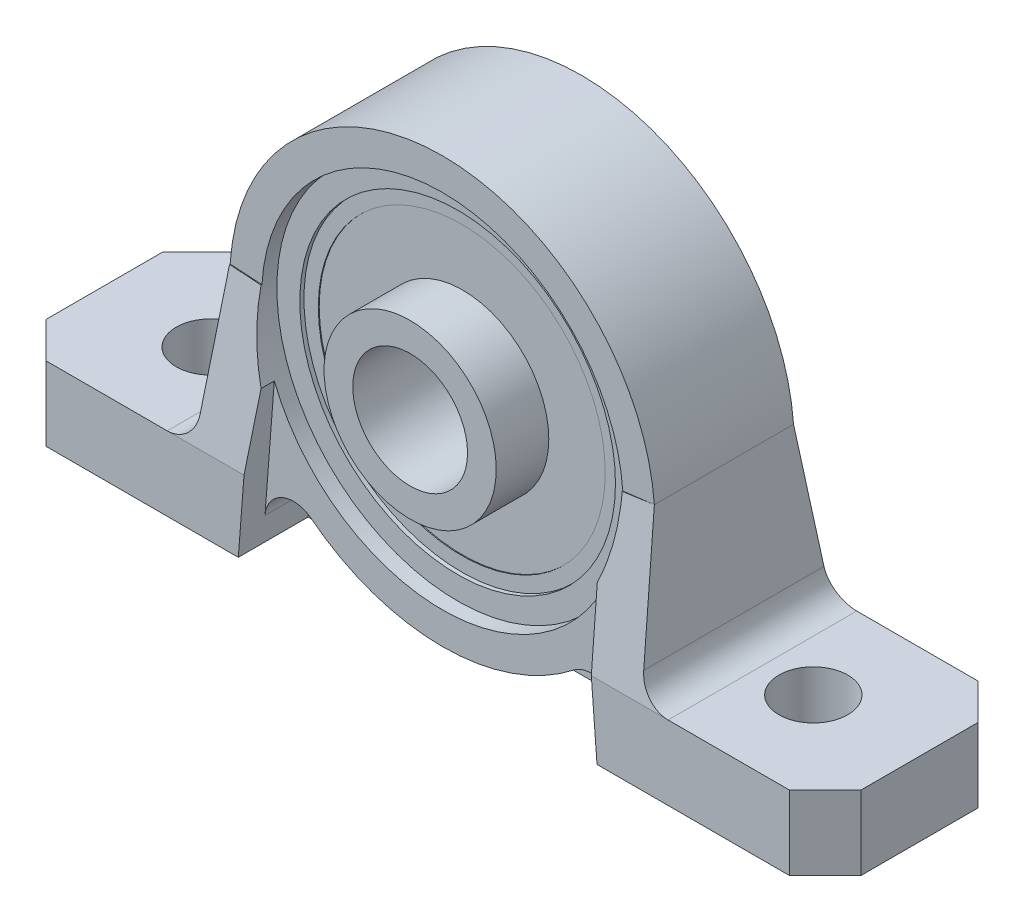
SolidWorks part; units mm, degrees
ref_plane "Front Plane" through (0, 0, 0) normal (0, 0, 1) x (1, 0, 0)
ref_plane "Top Plane" through (0, 0, 0) normal (0, 1, 0) x (1, 0, 0)
ref_plane "Right Plane" through (0, 0, 0) normal (1, 0, 0) x (0, 0, -1)
sketch "Sketch1" plane through (0, 0, 0) normal (1, 0, 0) x (0, 0, -1)
  line L0 (0, 17.3097) -> (0, -17.576) construction
  line L1 (0, 6) -> (-3.4358, 6)
  line L2 (-3.4358, 6) -> (-3.4358, 10)
  line L3 (-3.4358, 10) -> (3.4358, 10)
  line L4 (3.4358, 10) -> (3.4358, 6)
  line L5 (3.4358, 6) -> (0, 6)
  line L6 (-3.4358, 10) -> (-3.5, 10)
  line L7 (-3.5, 10) -> (-3.5, 11)
  line L8 (-3.5, 11) -> (0, 11)
  line L9 (0, 11) -> (3.5, 11)
  line L10 (3.5, 11) -> (3.5, 10)
  line L11 (3.5, 10) -> (3.4358, 10)
  line L12 (-11.6276, 0) -> (16.2204, 0) construction
  line L13 (3.4358, 6) -> (3.5, 6)
  line L14 (3.5, 6) -> (3.5, 4)
  line L15 (3.5, 4) -> (-7.0985, 4)
  line L16 (-7.0985, 4) -> (-7.0985, 6)
  line L17 (-7.0985, 6) -> (-3.4358, 6)
  line L18 (-3.5, 11) -> (-3.7892, 11)
  line L19 (-3.7892, 11) -> (-3.7892, 12.6)
  line L20 (-3.7892, 12.6) -> (0, 12.6)
  line L21 (0, 12.6) -> (3.7892, 12.6)
  line L22 (3.7892, 12.6) -> (3.7892, 11)
  line L23 (3.7892, 11) -> (3.5, 11)
  line L24 (-3.7892, 12.6) -> (-4.85, 12.6)
  line L25 (-4.85, 12.6) -> (-4.85, 14.815)
  line L26 (-4.85, 14.815) -> (0, 14.815)
  line L27 (0, 14.815) -> (4.85, 14.815)
  line L28 (4.85, 14.815) -> (4.85, 12.6)
  line L29 (4.85, 12.6) -> (3.7892, 12.6)
  point P15 (4.1728, 12.6)
  point P30 (3.7892, 12.6)
  point P31 (-4.85, 12.6)
  dimension "D1" = 7
  dimension "D2" = 22
  dimension "D3" = 8
  dimension "D4" = 2
  dimension "D5" = 1
  dimension "D6" = 1.6
  dimension "D7" = 29.63
  dimension "D8" = 9.7
revolve "Revolve1" add sketch "Sketch1" angle 360 about L12 region at (0, 5, 1.7993) region at (0, 8, 0) region at (0, 10.5, 0) region at (0, 11.8, 0) region at (0, 13.7075, 0)
sketch "Sketch2" plane through (0, 0, 0) normal (0, 0, 1) x (1, 0, 0)
  line L0 (0, 20.5844) -> (0, -27.498) construction
  line L1 (14.7714, 1.1362) -> (15.6015, -9.655)
  line L2 (15.6015, -9.655) -> (28.4021, -9.655)
  line L3 (28.4021, -9.655) -> (28.4021, -14.815)
  line L4 (28.4021, -14.815) -> (12.5, -14.815)
  line L5 (12.5, -14.815) -> (11.7155, -4.6375)
  line L6 (15.6015, -9.655) -> (12.1023, -9.655)
  line L7 (-15.6015, -9.655) -> (-12.1023, -9.655)
  line L8 (-12.5, -14.815) -> (-11.7155, -4.6375)
  line L9 (-28.4021, -14.815) -> (-12.5, -14.815)
  line L10 (-28.4021, -9.655) -> (-28.4021, -14.815)
  line L11 (-15.6015, -9.655) -> (-28.4021, -9.655)
  line L12 (-14.7714, 1.1362) -> (-15.6015, -9.655)
  line L13 (-12.5, -14.815) -> (12.5, -14.815) construction
  circle A0 centre (0, 0) radius 14.815 construction
  circle A1 centre (0, 0) radius 12.6 construction
  arc A2 (14.7714, 1.1362) -> (-14.7714, 1.1362) centre (0, 0) ccw
  arc A3 (11.7155, -4.6375) -> (-11.7155, -4.6375) centre (0, 0) ccw
  circle A4 centre (0, 0) radius 12.6 construction
  point P12 (0, -14.815)
  dimension "D3" = 5.16
  dimension "D4" = 25
extrude "Boss-Extrude1" add sketch "Sketch2" along normal mid plane 13.15 contours L2 L6 L5 L4 L3 | A2 L0 A3 L5 L6 L1 | L0 A2 L12 L7 L8 A3 | L7 L11 L10 L9 L8 region at (14.791, -4.2898, 0) region at (20.3512, -12.2244, 0) region at (-20.3512, -12.2244, 0)
sketch "Sketch8" plane through (0, -9.655, 0) normal (0, 1, 0) x (1, 0, 0)
  line L0 (-34.4299, 0) -> (37.1914, 0) construction
  line L1 (0, 17.012) -> (0, -19.2394) construction
  circle A0 centre (21, 0) radius 2.4
  circle A1 centre (-21, 0) radius 2.4
  dimension "D1" = 4.8
  dimension "D2" = 42
extrude "Cut-Extrude3" cut sketch "Sketch8" against normal through all
chamfer "Chamfer1" distance 2.5 angle 45 4 edges at (28.4021, -12.235, -6.575) (28.4021, -12.235, 6.575) (-28.4021, -12.235, -6.575) (-28.4021, -12.235, 6.575)
sketch "Sketch9" plane through (0, 0, 0) normal (0, 0, 1) x (1, 0, 0)
  line L0 (-12.5, -14.815) -> (12.5, -14.815)
  line L1 (12.5, -14.815) -> (11.7155, -4.6375)
  line L2 (-12.5, -14.815) -> (-11.7155, -4.6375)
  arc A0 (-11.7155, -4.6375) -> (11.7155, -4.6375) centre (0, 0) ccw
extrude "Boss-Extrude2" add sketch "Sketch9" along normal mid plane 3.42
fillet "Fillet1" radius 2 4 edges at (-12.0251, -8.6534, -3.28) (12.0251, -8.6534, -3.28) (-12.0251, -8.6534, 3.28) (12.0251, -8.6534, 3.28)
sketch "Sketch13" plane through (0, 0, 6.575) normal (0, 0, 1) x (1, 0, 0)
  line L0 (-11.89, 0.7057) -> (-17.6102, 1.0452)
  line L1 (-17.6102, 1.0452) -> (-14.4258, 15.1892)
  line L2 (-14.4258, 15.1892) -> (3.1299, 17.3837)
  line L3 (3.1299, 17.3837) -> (21.4172, 11.678)
  line L4 (21.4172, 11.678) -> (16.7844, 1.3884)
  line L5 (16.7844, 1.3884) -> (11.9408, 0.783)
  line L6 (11.9408, 0.783) -> (0.5941, 11.678)
  line L7 (0.5941, 11.678) -> (-11.89, 0.7057)
extrude "Cut-Extrude4" cut sketch "Sketch13" against normal up to surface (1.725 mm away) up to face at (0, -11.3237, 4.85)
extrude "Cut-Extrude5" cut sketch "Sketch13<2>" against normal through all from surface starting at face at (0, -11.3237, -4.85)
sketch "Sketch13<2>" plane through (0, 0, 6.575) normal (0, 0, 1) x (1, 0, 0) same geometry as "Sketch13"
sketch "Sketch14" plane through (0, 0, 0) normal (1, 0, 0) x (0, 0, -1)
  line L0 (-4.85, 1.1368) -> (-6.575, -9.655)
  line L1 (-6.575, -9.655) -> (-6.575, -14.815)
  line L2 (-6.575, -14.815) -> (6.575, -14.815)
  line L3 (6.575, -14.815) -> (6.575, -9.655)
  line L4 (6.575, -9.655) -> (4.85, 1.1368)
  line L6 (-4.85, 1.1368) -> (-4.85, 17.5008)
  line L7 (-4.85, 17.5008) -> (4.85, 17.5008)
  line L8 (4.85, 17.5008) -> (4.85, 1.1368)
extrude "Cut-Extrude-Thin5" cut sketch "Sketch14" along normal through all from offset 7 thin thin type one direction wall 10
extrude "Cut-Extrude-Thin6" cut sketch "Sketch14<2>" against normal through all from offset 7 thin offset against normal yes thin type one direction wall 10
sketch "Sketch14<2>" plane through (0, 0, 0) normal (1, 0, 0) x (0, 0, -1) same geometry as "Sketch14"
fillet "Fillet2" radius 2 2 edges at (-15.6015, -9.655, 0) (15.6015, -9.655, 0)
